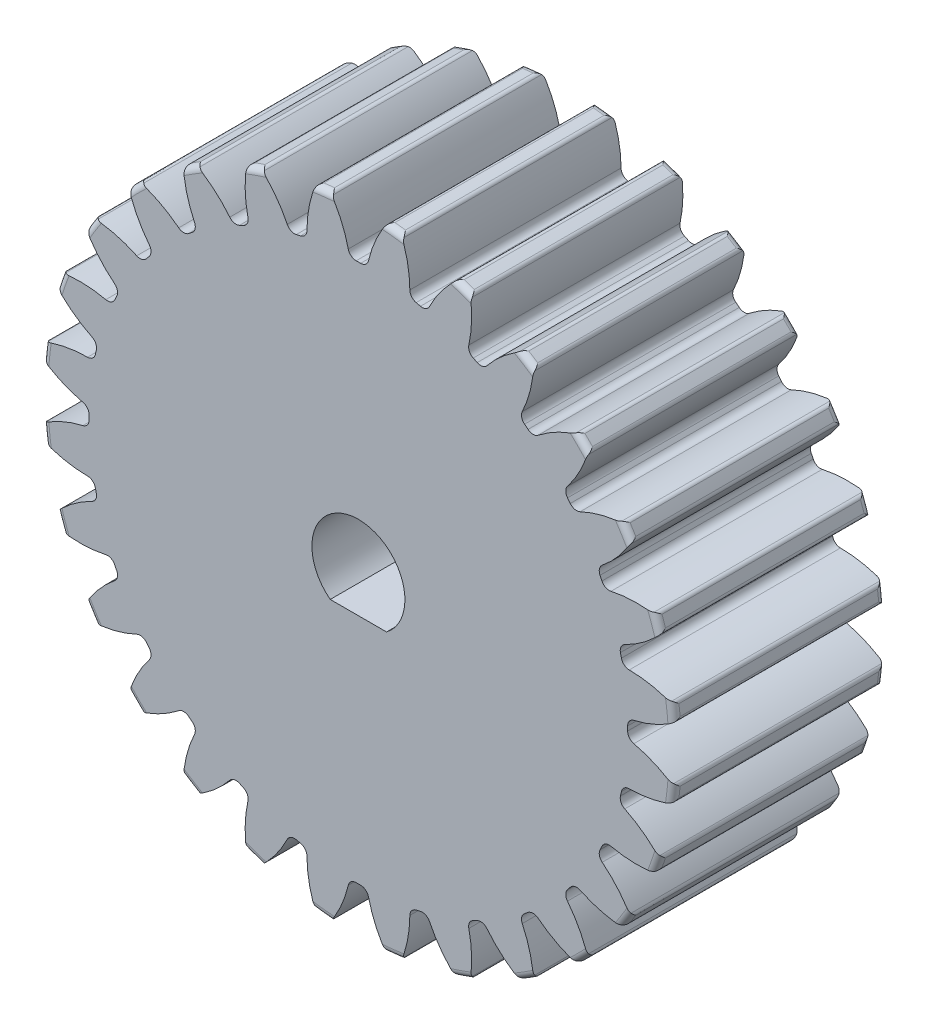
SolidWorks part; units mm, degrees
note: '?' marks a value the reader was unsure of.
ref_plane "Front Plane" through (0, 0, 0) normal (0, 0, 1) x (1, 0, 0)
ref_plane "Top Plane" through (0, 0, 0) normal (0, 1, 0) x (1, 0, 0)
ref_plane "Right Plane" through (0, 0, 0) normal (1, 0, 0) x (0, 0, -1)
sketch "Sketch1" plane through (0, 0, 0) normal (0, 0, 1) x (1, 0, 0)
  line L0 (-355.6, 0) -> (355.6, 0) construction
  line L1 (0, 0) -> (0, 5) construction
  circle A0 centre (0, 0) radius 22.5 construction
  circle A1 centre (0, 0) radius 21 construction
  circle A2 centre (0, 0) radius 19.125 construction
  circle A3 centre (0, 0) radius 18 construction
  circle A4 centre (0, 0) radius 5 construction
  point P9 (38.1, 0)
  dimension "D2" = 1.5
  dimension "D3" = 3.375
  dimension "D1" = 3.375
  dimension "Module" = 38.1
sketch "Sketch2" plane through (0, 0, 0) normal (1, 0, 0) x (0, 0, -1)
  line L0 (0, 0) -> (-15, 0) construction
  line L1 (-15, 0) -> (-29, 0) construction
  dimension "Overall Width" = 29
  dimension "Face Width" = 15
sketch "Sketch4" plane through (0, 0, 0) normal (1, 0, 0) x (0, 0, -1)
  line L0 (-29, 5) -> (-29, 18)
  line L1 (-29, 18) -> (-15, 18)
  line L2 (-15, 18) -> (-15, 22.5)
  line L3 (-15, 22.5) -> (0, 22.5)
  line L4 (0, 22.5) -> (0, 5)
  line L5 (-15, 18) -> (-15, 0) construction
  line L6 (0, 22.5) -> (0, -22.5) construction
  line L7 (-15, 18) -> (0, 18) construction
  line L12 (-29, 5) -> (0, 5)
revolve "Revolve1" add sketch "Sketch4" angle 360 about L1
fillet "Fillet2" radius 0.45 4 edges at (0, 18, 29) (0, 18, 15) (0, 22.5, 15) (0, 22.5, 0)
sketch "Sketch7" plane through (0, 0, 15) normal (0, 0, 1) x (1, 0, 0)
  line L0 (0, 0) -> (0, 22.5) construction
  line L1 (1.1775, 20.967) -> (1.8039, 22.4276) construction
  line L3 (2.5192, 22.3585) -> (2.3513, 20.868) construction
  line L4 (2.3513, 20.868) -> (2.1413, 19.0047) construction
  line L5 (0, 0) -> (2.1413, 19.0047) construction
  line L6 (1.1775, 20.967) -> (0, 0) construction
  line L7 (1.1775, 20.967) -> (1.2616, 22.4646) construction
  line L8 (1.1775, 20.967) -> (0, 0) construction
  circle A0 centre (0, 0) radius 22.5 construction
  circle A2 centre (0, 0) radius 19.125 construction
  arc A3 (-1.1775, 20.967) -> (1.1775, 20.967) centre (0, 0) cw construction
  circle A4 centre (0, 0) radius 21 construction
  arc A5 (3.0625, 22.2906) -> (1.9744, 22.4132) centre (0, 0) ccw construction
  arc A6 (1.1775, 20.967) -> (3.5176, 20.7033) centre (0, 0) cw construction
  arc A7 (-1.9744, 22.4132) -> (1.9744, 22.4132) centre (0, 0) cw
  arc A8 (0.625, 19.1148) -> (1.9744, 22.4132) centre (8.8974, 17.6559) cw
  arc A9 (-0.625, 19.1148) -> (-1.9744, 22.4132) centre (-8.8974, 17.6559) ccw
  arc A10 (0.625, 19.1148) -> (-0.625, 19.1148) centre (0, 0) ccw
  point P26 (-0.625, 19.1148)
  point P29 (0.625, 19.1148)
  dimension "D5" = 8.4
  dimension "D3" = 20
  dimension "D1" = 4.7124
  dimension "D2" = 2.3562
extrude "Cut-Extrude2" cut sketch "Sketch7" against normal through all
fillet "Fillet3" radius 0.57 2 edges at (0.625, 19.1148, 7.5) (-0.625, 19.1148, 7.5)
fillet "Fillet4" radius 0.285 2 edges at (1.9744, 22.4132, 7.5) (-1.9744, 22.4132, 7.5)
pattern_circular "CirPattern1" count 28 over 360 about axis through (0, 0, 0) along (0, 0, 1) of "Cut-Extrude2", "Fillet3", "Fillet4"
chamfer "Chamfer1" distance 0.2 angle 45 2 edges at (0, 5, 0) (0, 5, 29)
ref_plane "Contact Plane 1" through (0, 0, 29) normal (0, 0, 1) x (1, 0, 0)
ref_plane "Contact Plane 2" through (0, 0, 0) normal (0, 0, -1) x (-1, 0, 0)
ref_plane "Contact Plane 3" through (0, 0, 15) normal (0, 0, 1) x (1, 0, 0)
ref_axis "Cemter Axis 1" through (0, 0, 28.8) along (0, 0, -1)?
sketch "Esquisse1" plane through (0, 0, 29) normal (0, 0, 1) x (1, 0, 0)
  circle A0 centre (0, 0) radius 18.762
  circle A1 centre (0, 0) radius 18 construction
  dimension "D1" = 0.762
extrude "Enlèv. mat.-Extru.1" cut sketch "Esquisse1" against normal up to surface (14 mm away)
sketch "Esquisse2" plane through (0, 0, 15) normal (0, 0, 1) x (1, 0, 0)
  circle A0 centre (0, 0) radius 7.1467
extrude "Boss.-Extru.1" add sketch "Esquisse2" against normal up to surface (15 mm away) up to face at (0, 5.2, 0)
sketch "Esquisse3" plane through (0, 0, 15) normal (0, 0, 1) x (1, 0, 0)
  line L0 (-2, -2.6274) -> (2, -2.6274)
  arc A0 (2, -2.6274) -> (-2, -2.6274) centre (0, 0) ccw
  dimension "D2" = 3.302
  dimension "D1" = 4
extrude "Enlèv. mat.-Extru.2" cut sketch "Esquisse3" against normal through all
equation "\"D1@CirPattern1\"=\"Number of Teeth@Sketch1\""
equation "\"D1@Fillet2\"=\"OD@Sketch1\"*.01"
equation "\"D1@Sketch7\"=3.14159*(\"Pitch Dia.@Sketch1\"/\"Number of Teeth@Sketch1\")"
equation "\"D2@Sketch7\"=\"D1@Sketch7\"/2"
equation "\"D1@Sketch1\"=2.25mm*\"Module@Sketch1\""
equation "\"D1@Fillet3\"=.38mm*\"Module@Sketch1\""
equation "\"D1@Fillet4\"=\"D1@Fillet3\"/2"
equation "\"D5@Sketch7\"=\"Pitch Dia.@Sketch1\"/5"
